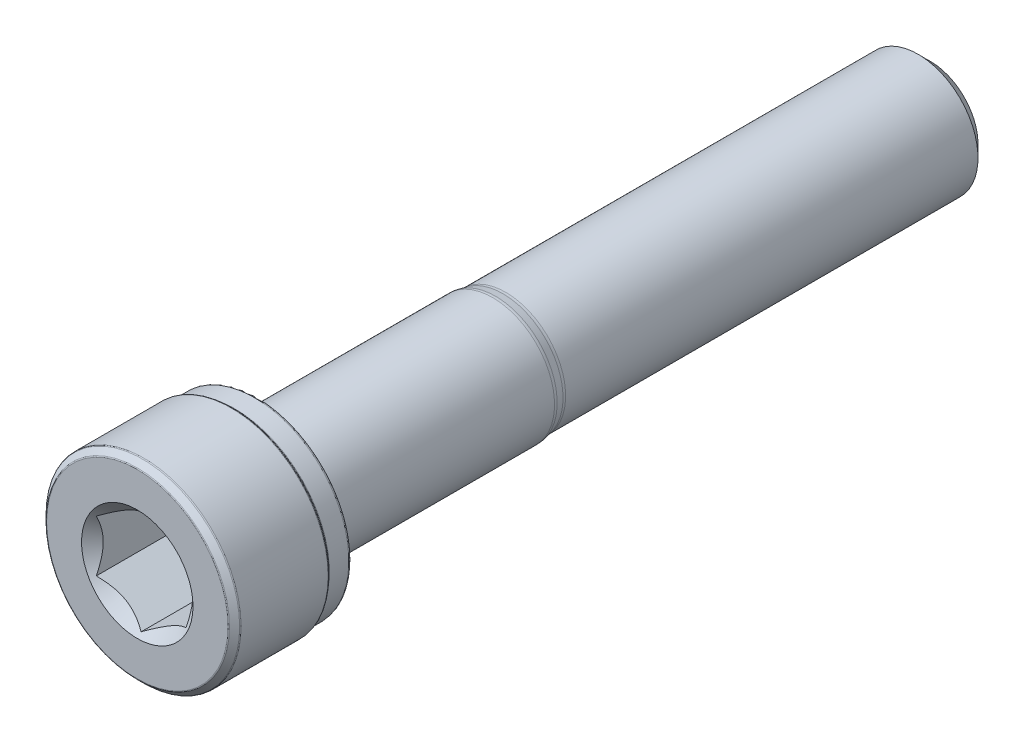
SolidWorks part; units mm, degrees
ref_plane "Front Plane" through (0, 0, 0) normal (0, 0, 1) x (1, 0, 0)
ref_plane "Top Plane" through (0, 0, 0) normal (0, 1, 0) x (1, 0, 0)
ref_plane "Right Plane" through (0, 0, 0) normal (1, 0, 0) x (0, 0, -1)
sketch "Sketch1" plane through (0, 0, 0) normal (1, 0, 0) x (0, 0, -1)
  line L0 (-26.5, 0) -> (26.5, 0) construction
  line L1 (26.5, 0) -> (26.5, 3.1881) construction
  line L2 (26.5, 3.1881) -> (25.6881, 4) construction
  line L3 (25.6881, 4) -> (25.5625, 4) construction
  line L4 (25.5625, 4) -> (-18.5, 4) construction
  line L5 (-18.5, 4) -> (-18.5, 6.5) construction
  line L6 (-18.5, 6.5) -> (-26.5, 6.5) construction
  line L7 (-26.5, 6.5) -> (-26.5, 0) construction
  line L8 (26.5, 3.1881) -> (26.5, 4) construction
  line L9 (26.4219, 4.1353) -> (27.0469, 3.0528) construction
  line L10 (27.0469, 3.0528) -> (27.6719, 4.1353) construction
  line L11 (27.6719, 4.1353) -> (26.4219, 4.1353) construction
  line L12 (27.0469, 4.1353) -> (27.0469, 4) construction
  line L13 (27.0469, 3.0528) -> (27.0469, 3.1881) construction
  line L14 (26.9688, 3.1881) -> (27.125, 3.1881) construction
  line L15 (26.5, 4) -> (27.5937, 4) construction
  line L16 (26.4609, 4.0677) -> (27.6328, 4.0677) construction
  line L17 (26.5, 0) -> (26.5, -4) construction
  line L18 (-18.9, 6.5) -> (-18.5, 6.1) construction
  line L19 (-26.1, 6.5) -> (-26.5, 6.1) construction
  line L20 (-18.5, 4) -> (-18.5, 0) construction
  line L21 (-18.5, 2) -> (-3.5, 2) construction
  line L22 (-3.5, 2) -> (11.5, 2) construction
  line L23 (11.5, 2) -> (26.5, 2) construction
  line L24 (-3.5, 2) -> (-3.5, 4) construction
  line L25 (-3.5, 4) -> (-3.5, 6.5) construction
  line L26 (11.5, 2) -> (11.5, 6.5) construction
  point P0 (-26.5, 3)
  point P3 (23.375, 4)
  point P4 (0, 0)
  point P18 (11.5, 4)
  point P22 (27.0469, 3.1881)
  point P24 (25.5625, 4)
  point P25 (27.0469, 4)
  point P28 (27.0469, 4.0677)
  point P29 (23.375, -4)
  point P30 (-3.5, 4)
  point P31 (-22.5, 6.5)
  point P37 (-19.9, 6.5)
  point P38 (-25.9, 6.5)
  point P45 (-3.5, 2)
  point P46 (11.5, 2)
  point P49 (-1.5, 4)
  dimension "D1" = 45
  dimension "D2" = 0.1562
  dimension "D7" = 0.4
  dimension "D8" = 0.4
  dimension "D9" = 0.4
  dimension "D10" = 0.2
  dimension "D11" = 1
  dimension "Drive Size" = 6
  dimension "Head Diameter" = 13
  dimension "Head Height" = 8
  dimension "Thread Pitch" = 1.25
  dimension "Thread Dia" = 8
  dimension "Length" = 45
  dimension "D12" = 0.9375
  dimension "D4" = 3.125
  dimension "Minimum Thread Length" = 28
sketch "Sketch2" plane through (0, 0, 0) normal (1, 0, 0) x (0, 0, -1)
  line L0 (-26.5, 0) -> (-26.5, 6.0586)
  line L1 (-26.0586, 6.5) -> (-20.2414, 6.5)
  line L2 (-18.5, 6.1375) -> (-18.5, 4.5353)
  line L4 (25.6881, 4) -> (26.5, 3.1881)
  line L5 (26.5, 3.1881) -> (26.5, 0)
  line L6 (-18.5, 6.5) -> (-26.5, 6.5) construction
  line L7 (26.5, 0) -> (-26.5, 0)
  line L8 (-26.1, 6.5) -> (-26.5, 6.1) construction
  line L10 (-26.1293, 6.4707) -> (-26.4707, 6.1293)
  line L12 (-19.9586, 6.3) -> (-18.6625, 6.3)
  line L14 (-18.9, 6.5) -> (-18.5, 6.1) construction
  line L15 (-20.1707, 6.4707) -> (-20.0293, 6.3293)
  line L17 (-18.5, 4) -> (-18.5, 6.5) construction
  line L18 (-18.1, 4.1353) -> (-2.7475, 4.1353)
  line L19 (-1.8703, 4) -> (25.6881, 4)
  line L20 (25.5625, 4) -> (-18.5, 4) construction
  line L21 (-2.5524, 4.1161) -> (-2.0653, 4.0192)
  line L22 (27.6719, 4.1353) -> (26.4219, 4.1353) construction
  arc A0 (-18.6625, 6.3) -> (-18.5, 6.1375) centre (-18.6625, 6.1375) cw
  arc A1 (-18.5, 4.5353) -> (-18.1, 4.1353) centre (-18.1, 4.5353) ccw
  arc A2 (-2.7475, 4.1353) -> (-2.5524, 4.1161) centre (-2.7475, 3.1353) cw
  arc A3 (-2.0653, 4.0192) -> (-1.8703, 4) centre (-1.8703, 5) ccw
  arc A4 (-26.1293, 6.4707) -> (-26.0586, 6.5) centre (-26.0586, 6.4) cw
  arc A5 (-26.4707, 6.1293) -> (-26.5, 6.0586) centre (-26.4, 6.0586) ccw
  arc A6 (-20.1707, 6.4707) -> (-20.2414, 6.5) centre (-20.2414, 6.4) ccw
  arc A7 (-20.0293, 6.3293) -> (-19.9586, 6.3) centre (-19.9586, 6.4) ccw
  point P22 (-18.7, 6.3)
  point P39 (-1.9688, 4)
  point P47 (-20, 6.3)
  dimension "D2" = 0.1625
  dimension "D3" = 0.4
  dimension "D6" = 1
  dimension "D7" = 0.1
  dimension "D1" = 1.5
  dimension "D4" = 11.25
  dimension "D5" = 0.4688
  dimension "D8" = 15.3525
revolve "Revolve1" add sketch "Sketch2" angle 360 about L7
sketch "Sketch3" plane through (0, 0, 26.5) normal (0, 0, 1) x (1, 0, 0)
  line L1 (3, -1.7321) -> (3, 1.7321)
  line L2 (3, 1.7321) -> (0, 3.4641)
  line L3 (0, 3.4641) -> (-3, 1.7321)
  line L4 (-3, 1.7321) -> (-3, -1.7321)
  line L5 (-3, -1.7321) -> (0, -3.4641)
  line L6 (0, -3.4641) -> (3, -1.7321)
  circle A0 centre (0, 0) radius 3 construction
  circle A1 centre (0, 0) radius 6.5 construction
  circle A2 centre (0, 0) radius 6.5 construction
  circle A3 centre (0, 0) radius 3.4641 construction
  dimension "D1" = 6.9282
extrude "Cut-Extrude1" cut sketch "Sketch3" against normal offset from surface (7 mm away) 1 up to face at (-6.1375, 0, 18.5)
sketch "Sketch4" plane through (0, 0, 26.5) normal (0, 0, 1) x (1, 0, 0)
  circle A0 centre (0, 0) radius 3.7239
  dimension "D1" = 7.4478
extrude "Cut-Extrude2" cut sketch "Sketch4" against normal up to vertex (4 mm away) draft 45 up to point (0, 6.5, 22.5)
sketch "Sketch11" plane through (0, 0, 0) normal (1, 0, 0) x (0, 0, -1)
  line L0 (-26.5, 0) -> (26.5, 0) construction
  line L1 (-26.5, 0) -> (26.5, 0) construction
  line L2 (-5.6261, -4) -> (-5.6261, 4) construction
  line L3 (25.5625, 4) -> (-18.5, 4) construction
  line L4 (-14.6619, -4) -> (-14.6619, 4) construction
  line L5 (-2.7475, 4.1353) -> (-2.7475, -4.1353) construction
  point P7 (-5.6261, 0)
  point P10 (-14.6619, 0)
  dimension "D1" = 3.8381
  dimension "D2" = 2.8786
sketch "Sketch6" [suppressed] plane through (0, 0, -26.5) normal (0, 0, -1) x (-1, 0, 0)
  circle A0 centre (0, 0) radius 4
curve "Helix/Spiral1" [suppressed] pitch 1.25 height 29.25 turns 23.4
sketch "Sketch10" [suppressed] plane through (0, 0, 0) normal (1, 0, 0) x (0, 0, -1)
  line L0 (-1.5, -4) -> (-1.5, 4)
  line L2 (-26.5, 0) -> (26.5, 0) construction
  point P3 (-1.5, 0)
split "Split1" [suppressed] bodies to split 106
sketch "Sketch7" [suppressed] plane through (0, 0, 0) normal (1, 0, 0) x (0, 0, -1)
  line L0 (26.4609, 4.0677) -> (27.6328, 4.0677)
  line L1 (27.6328, 4.0677) -> (27.125, 3.1881)
  line L2 (27.125, 3.1881) -> (26.9688, 3.1881)
  line L3 (26.9688, 3.1881) -> (26.4609, 4.0677)
sweep "Cut-Sweep1" [suppressed] cut profiles "Sketch7" path "Helix/Spiral1"
sketch "Sketch8" [suppressed] plane through (0, 0, 0) normal (1, 0, 0) x (0, 0, -1)
  line L0 (-18.5, 0) -> (-18.5, 4)
  line L2 (-18.5, 4) -> (-1.5, 4)
  line L4 (-1.5, 4) -> (0.8094, 0)
  line L5 (0.8094, 0) -> (-18.5, 0)
  line L6 (25.5625, 4) -> (-18.5, 4) construction
  line L7 (-26.5, 0) -> (26.5, 0) construction
  dimension "D1" = 60
  dimension "D2" = 28
revolve "Revolve2" [suppressed] add sketch "Sketch8" angle 360 about L5
sketch "Sketch9" [suppressed] plane through (0, 0, 26.5) normal (0, 0, 1) x (1, 0, 0)
  line L0 (-0.0297, 6.3662) -> (-0.1625, 6.6628)
  line L1 (-0.1625, 6.6628) -> (0.1625, 6.6628)
  line L2 (0.1625, 6.6628) -> (0.0297, 6.3662)
  line L3 (0, 6.5) -> (0, 6.1) construction
  line L4 (0, 0) -> (-0.1625, 6.6628) construction
  line L5 (0.1625, 6.6628) -> (0, 0) construction
  circle A0 centre (0, 0) radius 6.3 construction
  arc A4 (-0.0297, 6.3662) -> (0.0297, 6.3662) centre (0, 6.3795) ccw
  point P10 (0, 6.3)
  point P19 (0, 6.3)
  dimension "D2" = 0.0325
  dimension "D1" = 0.325
  dimension "D3" = 2.794
extrude "Cut-Extrude3" [suppressed] cut sketch "Sketch9" against normal through all
pattern_circular "CirPattern1" [suppressed] count 80 over 360 of bodies 112
equation "\"D2@Sketch1\" = \"Thread Pitch@Sketch1\" / 8"
equation "\"D4@Helix/Spiral1\" = \"Thread Pitch@Sketch1\""
equation "\"D7@Sketch1\" = \"Head Height@Sketch1\" * .05"
equation "\"D8@Sketch1\"=\"D7@Sketch1\""
equation "\"D9@Sketch1\"=\"D7@Sketch1\""
equation "\"D10@Sketch1\"=\"D7@Sketch1\"/2"
equation "\"D11@Sketch1\"=\"D10@Sketch1\"*5"
equation "\"D4@Sketch1\"=\"Thread Pitch@Sketch1\"*2.5"
equation "\"D12@Sketch1\"=\"Thread Pitch@Sketch1\"*.75"
equation "\"D3@Helix/Spiral1\"=\"Minimum Thread Length@Sketch1\"+\"Thread Pitch@Sketch1\""
equation "\"D2@Sketch8\"=\"Minimum Thread Length@Sketch1\""
equation "\"D1@Sketch2\"=\"Head Height@Sketch1\"*0.1875"
equation "\"D2@Sketch2\"=\"Head Diameter@Sketch1\"*0.0125"
equation "\"D3@Sketch2\"=\"Thread Dia@Sketch1\"*0.05"
equation "\"D1@Sketch9\"=\"Head Diameter@Sketch1\"*0.025"
equation "\"D2@Sketch9\"=\"D1@Sketch9\"*0.1"
equation "\"D1@CirPattern1\"=int ((360/\"D3@Sketch9\")*0.625)"
equation "\"D5@Sketch2\"=\"D12@Sketch1\"*0.5"
equation "\"D6@Sketch2\"=\"Thread Dia@Sketch1\"*0.125"
equation "\"D7@Sketch2\"=\"D8@Sketch1\"*0.25"
equation "\"D1@Sketch11\"=\"D8@Sketch2\"*0.25"
equation "\"D2@Sketch11\"=\"D8@Sketch2\"*0.1875"
equation "\"D1@Sketch4\"=\"D1@Sketch3\"*1.075"
